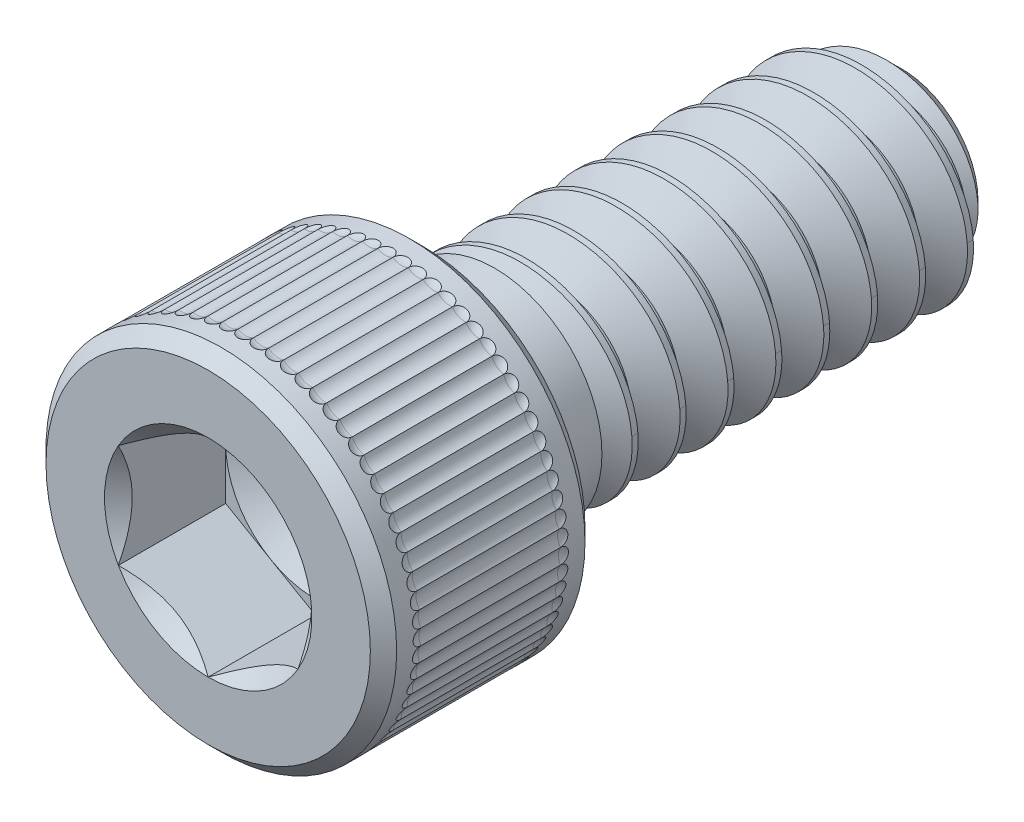
SolidWorks part; units mm, degrees
ref_plane "Front Plane" through (0, 0, 0) normal (0, 0, 1) x (1, 0, 0)
ref_plane "Top Plane" through (0, 0, 0) normal (0, 1, 0) x (1, 0, 0)
ref_plane "Right Plane" through (0, 0, 0) normal (1, 0, 0) x (0, 0, -1)
sketch "Sketch1" plane through (0, 0, 0) normal (1, 0, 0) x (0, 0, -1)
  line L0 (4.5974, 0) -> (-4.5974, 0) construction
  line L1 (-4.5974, -2.3241) -> (-4.5974, 2.3241) construction
  line L2 (-4.5974, 2.3241) -> (-1.7526, 2.3241) construction
  line L3 (4.5974, -1.4224) -> (4.5974, 1.4224) construction
  line L7 (4.5577, 1.4911) -> (5.1927, 1.4911) construction
  line L8 (5.1927, 1.4911) -> (4.8752, 0.9412) construction
  line L9 (4.8752, 0.9412) -> (4.5577, 1.4911) construction
  line L10 (4.8752, 1.4911) -> (4.8752, 1.4224) construction
  line L11 (4.8752, 1.4224) -> (4.8752, 1.01) construction
  line L12 (4.8752, 1.01) -> (4.8752, 0.9412) construction
  line L13 (4.8355, 1.01) -> (4.9149, 1.01) construction
  line L14 (4.5974, 1.4224) -> (5.153, 1.4224) construction
  line L15 (4.5776, 1.4568) -> (5.1729, 1.4568) construction
  line L17 (4.5974, -1.4224) -> (3.0099, -1.4224) construction
  point P4 (0, 0)
  point P8 (-4.5974, 0)
  point P11 (4.5974, 0)
  point P16 (-4.5974, 1.1906)
  point P20 (4.8752, 1.01)
  point P23 (4.8752, 1.4224)
  point P26 (4.8752, 1.4568)
  point P27 (-4.5974, -1.1906)
  dimension "Head Diameter" = 4.6482
  dimension "Head Height" = 2.8448
  dimension "Length" = 6.35
  dimension "Screw Size Decimal Equivalent" = 2.8448
  dimension "Thread Pitch" = 0.635
  dimension "D1" = 0.0794
  dimension "Drive Size" = 2.3813
  dimension "D2" = 1.5875
sketch "Sketch2" plane through (0, 0, 0) normal (1, 0, 0) x (0, 0, -1)
  line L0 (-1.9269, 2.3241) -> (-1.7526, 2.1498)
  line L1 (-4.5974, 2.3241) -> (-1.7526, 2.3241) construction
  line L2 (-4.5974, 1.1906) -> (-3.175, 1.1906)
  line L3 (-3.175, 1.1906) -> (-3.175, 0)
  line L4 (4.5974, 0) -> (-4.5974, 0) construction
  line L5 (-3.175, 0) -> (4.5974, 0)
  line L6 (4.5974, 0) -> (4.5974, 1.01)
  line L7 (4.5974, -1.4224) -> (4.5974, 1.4224) construction
  line L8 (4.5974, 1.01) -> (4.185, 1.4224)
  line L9 (4.185, 1.4224) -> (-1.6104, 1.4224)
  line L10 (-1.7526, 1.5646) -> (-1.7526, 2.1498)
  line L11 (-4.5974, 1.1906) -> (-4.5974, 2.1498)
  line L12 (-4.5974, -2.3241) -> (-4.5974, 2.3241) construction
  line L13 (-4.5974, 2.1498) -> (-4.4231, 2.3241)
  line L14 (-4.4231, 2.3241) -> (-1.9269, 2.3241)
  arc A0 (-1.6104, 1.4224) -> (-1.7526, 1.5646) centre (-1.6104, 1.5646) cw
  point P24 (-1.7526, 1.4224)
  dimension "D6" = 0.1422
  dimension "D1" = 45
  dimension "D3" = 1.4224
  dimension "D4" = 45
  dimension "D5" = 0.1743
  dimension "D2" = 0.1743
revolve "Revolve1" add sketch "Sketch2" angle 360 about L5
sketch "Sketch3" plane through (0, 0, 4.5974) normal (0, 0, 1) x (1, 0, 0)
  line L5 (0, 1.3748) -> (-1.1906, 0.6874)
  line L7 (-1.1906, 0.6874) -> (-1.1906, -0.6874)
  line L8 (-1.1906, -0.6874) -> (0, -1.3748)
  line L9 (0, -1.3748) -> (1.1906, -0.6874)
  line L10 (1.1906, -0.6874) -> (1.1906, 0.6874)
  line L11 (1.1906, 0.6874) -> (0, 1.3748)
  circle A1 centre (0, 0) radius 1.1906 construction
  circle A2 centre (0, 0) radius 1.1906 construction
extrude "Cut-Extrude1" cut sketch "Sketch3" against normal up to surface (1.4224 mm away) up to face at (1.1906, 0, 3.175)
sketch "Sketch4" plane through (0, 0, 4.5974) normal (0, 0, 1) x (1, 0, 0)
  circle A0 centre (0, 0) radius 1.3748
extrude "Cut-Extrude2" cut sketch "Sketch4" against normal through all draft 45
sketch "Sketch6" plane through (0, 0, 3.175) normal (0, 0, 1) x (1, 0, 0)
  line L0 (-1.1906, 0.6874) -> (-1.1906, -0.6874) construction
  circle A1 centre (0, 0) radius 1.1906
extrude "Cut-Extrude5" cut sketch "Sketch6" against normal through all draft 60
sketch "Sketch7" plane through (0, 0, -4.5974) normal (0, 0, -1) x (-1, 0, 0)
  circle A0 centre (0, 0) radius 1.4224
curve "Helix/Spiral1" pitch 0.635 height 6.7469 turns 10.625
sketch "Sketch8" plane through (0, 0, 0) normal (1, 0, 0) x (0, 0, -1)
  line L0 (4.5776, 1.4568) -> (5.1729, 1.4568)
  line L1 (5.1729, 1.4568) -> (4.9149, 1.01)
  line L2 (4.9149, 1.01) -> (4.8355, 1.01)
  line L3 (4.8355, 1.01) -> (4.5776, 1.4568)
sweep "Cut-Sweep1" cut profiles "Sketch8" path "Helix/Spiral1"
sketch "Sketch9" plane through (0, 0, 0) normal (1, 0, 0) x (0, 0, -1)
  line L0 (-2.1892, 0) -> (-2.1892, 1.5646)
  line L1 (4.5974, 0) -> (-4.5974, 0) construction
  line L2 (-1.6104, 1.4224) -> (-0.8001, 1.4224)
  line L3 (-0.8001, 1.4224) -> (0.0211, 0)
  line L4 (0.0211, 0) -> (-2.1892, 0)
  line L5 (4.5974, 1.4224) -> (5.153, 1.4224) construction
  line L8 (-3.175, 0) -> (4.5974, 0) construction
  line L9 (4.5974, 0) -> (4.5974, 1.01) construction
  line L10 (-2.1892, 1.5646) -> (-1.7526, 1.5646)
  arc A0 (-1.7526, 1.5646) -> (-1.6104, 1.4224) centre (-1.6104, 1.5646) ccw construction
  arc A1 (-1.7526, 1.5646) -> (-1.6104, 1.4224) centre (-1.6104, 1.5646) ccw
  dimension "D1" = 60
  dimension "D3" = 6.7866
  dimension "D2" = 0.9525
revolve "Revolve2" add sketch "Sketch9" angle 360 about L4
ref_plane "Plane1" through (0, 0, 3.175) normal (0, 0, -1) x (-1, 0, 0)
sketch "Sketch11" plane through (0, 0, 3.175) normal (0, 0, -1) x (-1, 0, 0)
  line L0 (0, 0) -> (0.1014, 2.3219) construction
  line L1 (0.1014, 2.3219) -> (-0.1014, 2.3219) construction
  line L2 (-0.1014, 2.3219) -> (0, 0) construction
  line L3 (0.1014, 2.3219) -> (0, 2.2634) construction
  line L4 (0, 2.2634) -> (-0.1014, 2.3219) construction
  circle A0 centre (0, 2.4975) radius 0.2028
  circle A1 centre (0, 0) radius 2.3241 construction
  dimension "D1" = 5
  dimension "D2" = 120
sketch "Sketch12" plane through (0, 0, 0) normal (1, 0, 0) x (0, 0, -1)
  line L0 (-4.0996, 2.2947) -> (-2.2504, 2.2947)
  line L1 (-4.3023, 2.4975) -> (-2.0477, 2.4975)
  arc A0 (-2.2504, 2.2947) -> (-2.0477, 2.4975) centre (-2.2504, 2.4975) ccw
  arc A1 (-4.0996, 2.2947) -> (-4.3023, 2.4975) centre (-4.0996, 2.4975) cw
  point P3 (-3.175, 2.4975)
  point P11 (-3.175, 2.2947)
  dimension "D1" = 1.8491
revolve "Cut-Revolve1" cut sketch "Sketch12" angle 360 about L1
pattern_circular "CirPattern1" count 72 over 360 about axis through (0, 0, 0) along (0, 0, 1) of "Cut-Revolve1"
equation "\"D1@Sketch1\"=\"Thread Pitch@Sketch1\"/8"
equation "\"D5@Sketch2\"=\"D2@Sketch2\""
equation "\"D3@Helix/Spiral1\"=\"Length@Sketch1\"+\"Thread Pitch@Sketch1\"*0.625"
equation "\"D4@Helix/Spiral1\"=\"Thread Pitch@Sketch1\""
equation "\"D2@Sketch2\"=\"Head Diameter@Sketch1\"*0.0375"
equation "\"D2@Sketch1\"=\"Thread Pitch@Sketch1\"*2.5"
equation "\"D3@Sketch2\"=\"Head Height@Sketch1\"*0.5"
equation "\"60g\"=45"
equation "\"D6@Sketch2\" = \"Screw Size Decimal Equivalent@Sketch1\" * 0.05"
equation "\"D3@Sketch9\"=\"D3@Helix/Spiral1\"+\"D1@Sketch1\"*0.5"
equation "\"D2@Sketch9\"=\"Thread Pitch@Sketch1\"*1.5"
equation "\"D1\"= \"Head Height@Sketch1\" * 0.075"
equation "\"D1@Sketch12\"=\"Head Height@Sketch1\"*.65"
equation "\"D1@CirPattern1\"=360/\"D1@Sketch11\""
